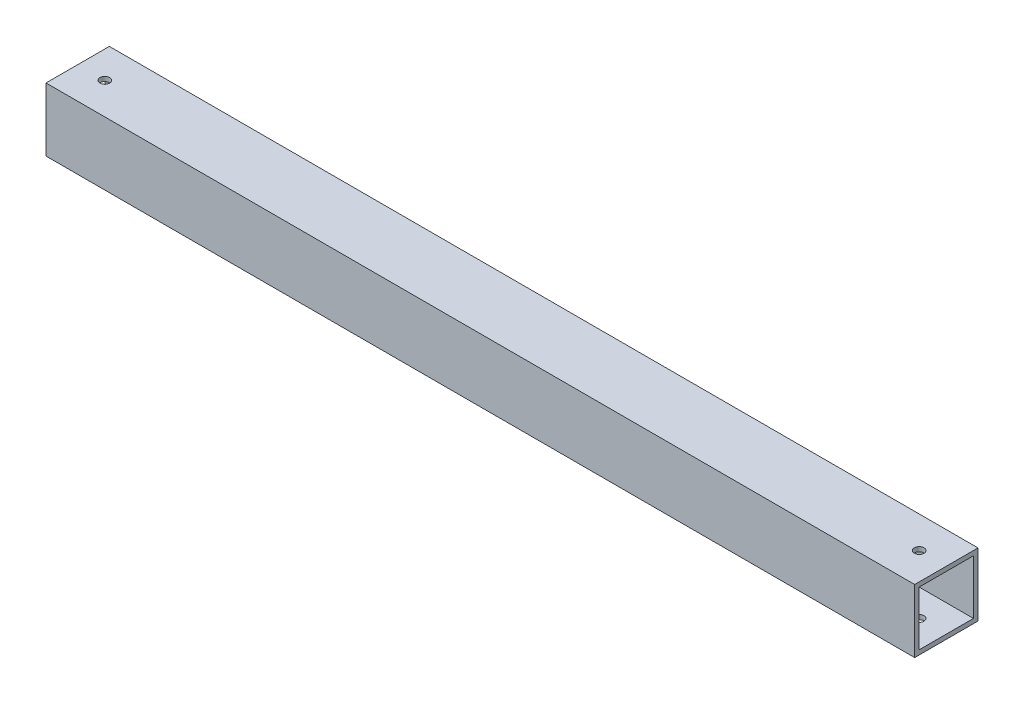
SolidWorks part; units mm, degrees
material "6061 Alloy"
ref_plane "Front Plane" through (0, 0, 0) normal (0, 0, 1) x (1, 0, 0)
ref_plane "Top Plane" through (0, 0, 0) normal (0, 1, 0) x (1, 0, 0)
ref_plane "Right Plane" through (0, 0, 0) normal (1, 0, 0) x (0, 0, -1)
sketch "Sketch1" plane through (0, 0, 0) normal (1, 0, 0) x (0, 0, -1)
  line L0 (-19.05, 19.05) -> (19.05, 19.05)
  line L1 (-22.225, -22.225) -> (22.225, -22.225)
  line L2 (-22.225, -22.225) -> (-22.225, 22.225)
  line L3 (-22.225, 22.225) -> (22.225, 22.225)
  line L4 (22.225, -22.225) -> (22.225, 22.225)
  line L5 (-22.225, -22.225) -> (22.225, 22.225) construction
  line L6 (-22.225, 22.225) -> (22.225, -22.225) construction
  line L7 (19.05, -19.05) -> (19.05, 19.05)
  line L8 (-19.05, -19.05) -> (19.05, -19.05)
  line L9 (-19.05, -19.05) -> (-19.05, 19.05)
  point P0 (0, 0)
  dimension "D1" = 44.45
  dimension "D2" = 3.175
extrude "Boss-Extrude1" add sketch "Sketch1" along normal blind 609.6
hole_wizard "1/4 Clearance Hole1" positions "Sketch2" profile "Sketch3" hole size "1/4" standard "ANSI Inch" end condition through all
sketch "Sketch2" plane through (0, 22.225, 0) normal (0, 1, 0) x (1, 0, 0)
  line L0 (304.8, 22.225) -> (304.8, -22.225) construction
  line L1 (609.6, 22.225) -> (0, 22.225) construction
  line L2 (609.6, -22.225) -> (0, -22.225) construction
  line L3 (0, 0) -> (609.6, 0) construction
  line L4 (0, 22.225) -> (0, -22.225) construction
  line L5 (609.6, 22.225) -> (609.6, -22.225) construction
  point P0 (19.05, 0)
  point P10 (590.55, 0)
  dimension "D1" = 19.05
sketch "Sketch3" plane through (19.05, 22.225, 0) normal (1, 0, 0) x (0, 0, 1)
  line L0 (0, 0) -> (0, 44.45)
  line L1 (0, 44.45) -> (3.3782, 44.45)
  line L2 (3.3782, 44.45) -> (3.3782, 0)
  line L5 (3.3782, 0) -> (0, 0)
  line L11 (0, -6.35) -> (0, 107.95) construction
  dimension "Thru Hole Dia." = 6.7564
  dimension "Thru Hole Depth" = 44.45
